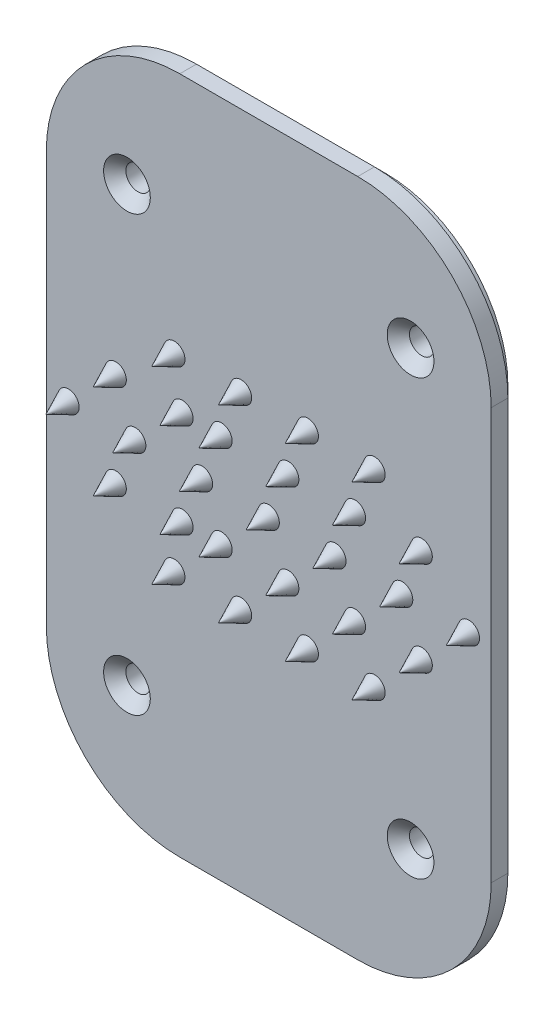
SolidWorks part; units mm, degrees
ref_plane "前视基准面" through (0, 0, 0) normal (0, 0, 1) x (1, 0, 0)
ref_plane "上视基准面" through (0, 0, 0) normal (0, 1, 0) x (1, 0, 0)
ref_plane "右视基准面" through (0, 0, 0) normal (1, 0, 0) x (0, 0, -1)
sketch "草图3" plane through (0, 0, 0) normal (0, 0, 1) x (1, 0, 0)
  line L0 (0, 28.5) -> (0, -28.5) construction
  line L2 (21, 0) -> (-21, 0) construction
  line L4 (7, 28.5) -> (-7, 28.5)
  line L5 (-18, 17.5) -> (-18, -17.5)
  line L7 (18, 17.5) -> (18, -17.5)
  line L8 (7, -28.5) -> (-7, -28.5)
  arc A0 (-7, 28.5) -> (-18, 17.5) centre (-7, 17.5) ccw
  arc A1 (7, 28.5) -> (18, 17.5) centre (7, 17.5) cw
  arc A2 (7, -28.5) -> (18, -17.5) centre (7, -17.5) ccw
  arc A3 (-7, -28.5) -> (-18, -17.5) centre (-7, -17.5) cw
  circle A4 centre (-12.75, 19.5259) radius 2.1
  circle A5 centre (12.75, 19.5259) radius 2.1
  circle A6 centre (12.75, -19.5) radius 2.1
  circle A7 centre (-12.75, -19.5) radius 2.1
  point P20 (-18, 0)
  point P22 (0, 0)
  point P28 (18, 0)
extrude "凸台-拉伸1" add sketch "草图3" along normal blind 1
sketch "草图5" plane through (0, 0, 1) normal (0, 0, 1) x (1, 0, 0)
  line L0 (0, 30.5) -> (0, -30.5) construction
  line L1 (19, 17.5) -> (19, -17.5)
  line L2 (8, 30.5) -> (-8, 30.5) construction
  line L3 (21, 0) -> (-21, 0) construction
  line L4 (-21, 19.5) -> (-21, -19.5) construction
  line L5 (-7, 29.5) -> (7, 29.5)
  line L6 (7, 29.5) -> (-7, 29.5) construction
  line L7 (-19, 17.5) -> (-19, -17.5)
  line L8 (-19, 17.5) -> (-19, -17.5) construction
  line L9 (-7, -29.5) -> (7, -29.5)
  arc A0 (-7, 29.5) -> (-19, 17.5) centre (-7, 17.5) ccw
  arc A1 (7, 29.5) -> (19, 17.5) centre (7, 17.5) cw
  arc A2 (7, -29.5) -> (19, -17.5) centre (7, -17.5) ccw
  arc A3 (-7, -29.5) -> (-19, -17.5) centre (-7, -17.5) cw
  circle A4 centre (-12.75, 19.5259) radius 1.1
  circle A5 centre (12.75, 19.5259) radius 1.1
  circle A6 centre (12.75, -19.5) radius 1.1
  circle A7 centre (-12.75, -19.5) radius 1.1
  point P17 (19, 0)
  point P23 (0, -29.5)
  point P24 (0, 29.5)
  point P25 (0, 0)
  point P31 (-19, 0)
extrude "凸台-拉伸3" add sketch "草图5" along normal blind 1
sketch "草图7" plane through (0, 0, 2) normal (0, 0, 1) x (1, 0, 0)
  line L0 (-8, 30.5) -> (8, 30.5)
  line L1 (8, 30.5) -> (-8, 30.5) construction
  line L2 (-20, 18.5) -> (-20, -18.5)
  line L3 (-20, 18.5) -> (-20, -18.5) construction
  line L4 (0, 30.5) -> (0, -30.5) construction
  line L5 (20, 0) -> (-20, 0) construction
  line L6 (20, 18.5) -> (20, -18.5)
  line L7 (-8, -30.5) -> (8, -30.5)
  arc A0 (-8, 30.5) -> (-20, 18.5) centre (-8, 18.5) ccw
  arc A1 (8, 30.5) -> (20, 18.5) centre (8, 18.5) cw
  arc A2 (8, -30.5) -> (20, -18.5) centre (8, -18.5) ccw
  arc A3 (-8, -30.5) -> (-20, -18.5) centre (-8, -18.5) cw
  circle A4 centre (-12.75, 19.5259) radius 1.1
  circle A5 centre (12.75, 19.5259) radius 1.1
  circle A6 centre (12.75, -19.5) radius 1.1
  circle A7 centre (-12.75, -19.5) radius 1.1
  point P19 (0, 0)
extrude "凸台-拉伸4" add sketch "草图7" along normal blind 1.5
chamfer "倒角1" distance 1 angle 45 4 edges at (13.85, -19.5, 3.5) (-11.65, -19.5, 3.5) (-11.65, 19.5259, 3.5) (13.85, 19.5259, 3.5)
sketch "草图8" plane through (0, 0, 3.5) normal (0, 0, 1) x (1, 0, 0)
  line L0 (0, -17.325) -> (0, 17.325) construction
  line L1 (17.325, 0) -> (-17.325, 0) construction
  circle A0 centre (0, 0) radius 0.9512
  circle A1 centre (6, 0) radius 0.9512
  circle A2 centre (12, 0) radius 0.9512
  circle A3 centre (18, 0) radius 0.9512
  circle A4 centre (1.7574, 4.2426) radius 0.9512
  circle A5 centre (7.7574, 4.2426) radius 0.9512
  circle A6 centre (13.7574, 4.2426) radius 0.9512
  circle A7 centre (-2.4853, 8.4853) radius 0.9512
  circle A8 centre (3.5147, 8.4853) radius 0.9512
  circle A9 centre (9.5147, 8.4853) radius 0.9512
  circle A10 centre (-4.2426, 4.2426) radius 0.9512
  circle A11 centre (-8.4853, 8.4853) radius 0.9512
  circle A12 centre (-8.4853, -8.4853) radius 0.9512
  circle A13 centre (-4.2426, -4.2426) radius 0.9512
  circle A14 centre (9.5147, -8.4853) radius 0.9512
  circle A15 centre (3.5147, -8.4853) radius 0.9512
  circle A16 centre (-2.4853, -8.4853) radius 0.9512
  circle A17 centre (13.7574, -4.2426) radius 0.9512
  circle A18 centre (7.7574, -4.2426) radius 0.9512
  circle A19 centre (1.7574, -4.2426) radius 0.9512
  circle A20 centre (-7.7574, -4.2426) radius 0.9512
  circle A21 centre (-7.7574, 4.2426) radius 0.9512
  circle A22 centre (-6, 0) radius 0.9512
  circle A23 centre (-13.7574, -4.2426) radius 0.9512
  circle A24 centre (-13.7574, 4.2426) radius 0.9512
  circle A25 centre (-18, 0) radius 0.9512
  circle A26 centre (-12, 0) radius 0.9512
  dimension "D1" = 4
  dimension "D2" = 3
extrude "凸台-拉伸5" add sketch "草图8" along normal blind 2
chamfer "倒角2" distance 2 angle 25 27 edges at (8.5636, -8.4853, 5.5) (2.5636, -8.4853, 5.5) (0.8062, -4.2426, 5.5) (6.8062, -4.2426, 5.5) (12.8062, -4.2426, 5.5) (18.9512, 0, 5.5) (12.9512, 0, 5.5) (6.9512, 0, 5.5) (0.9512, 0, 5.5) (-18.9512, 0, 5.5) (-12.8062, -4.2426, 5.5) (-3.4364, -8.4853, 5.5) (-9.4364, -8.4853, 5.5) (-6.8062, -4.2426, 5.5) (-5.1938, -4.2426, 5.5) (-6.9512, 0, 5.5) (-12.9512, 0, 5.5) (-14.7085, 4.2426, 5.5) (-8.7085, 4.2426, 5.5) (-3.2915, 4.2426, 5.5) (2.7085, 4.2426, 5.5) (8.7085, 4.2426, 5.5) (14.7085, 4.2426, 5.5) (10.4659, 8.4853, 5.5) (4.4659, 8.4853, 5.5) (-1.5341, 8.4853, 5.5) (-7.5341, 8.4853, 5.5) first distance on face at (8.5636, -8.4853, 5.5) first distance on face at (2.5636, -8.4853, 5.5) first distance on face at (0.8062, -4.2426, 5.5) first distance on face at (6.8062, -4.2426, 5.5) first distance on face at (12.8062, -4.2426, 5.5) first distance on face at (18.9512, 0, 5.5) first distance on face at (12.9512, 0, 5.5) first distance on face at (6.9512, 0, 5.5) first distance on face at (0.9512, 0, 5.5) first distance on face at (-18.9512, 0, 5.5) first distance on face at (-12.8062, -4.2426, 5.5) first distance on face at (-3.4364, -8.4853, 5.5) first distance on face at (-9.4364, -8.4853, 5.5) first distance on face at (-6.8062, -4.2426, 5.5) first distance on face at (-5.1938, -4.2426, 5.5) first distance on face at (-6.9512, 0, 5.5) first distance on face at (-12.9512, 0, 5.5) first distance on face at (-14.7085, 4.2426, 5.5) first distance on face at (-8.7085, 4.2426, 5.5) first distance on face at (-3.2915, 4.2426, 5.5) first distance on face at (2.7085, 4.2426, 5.5) first distance on face at (8.7085, 4.2426, 5.5) first distance on face at (14.7085, 4.2426, 5.5) first distance on face at (10.4659, 8.4853, 5.5) first distance on face at (4.4659, 8.4853, 5.5) first distance on face at (-1.5341, 8.4853, 5.5) first distance on face at (-7.5341, 8.4853, 5.5)
